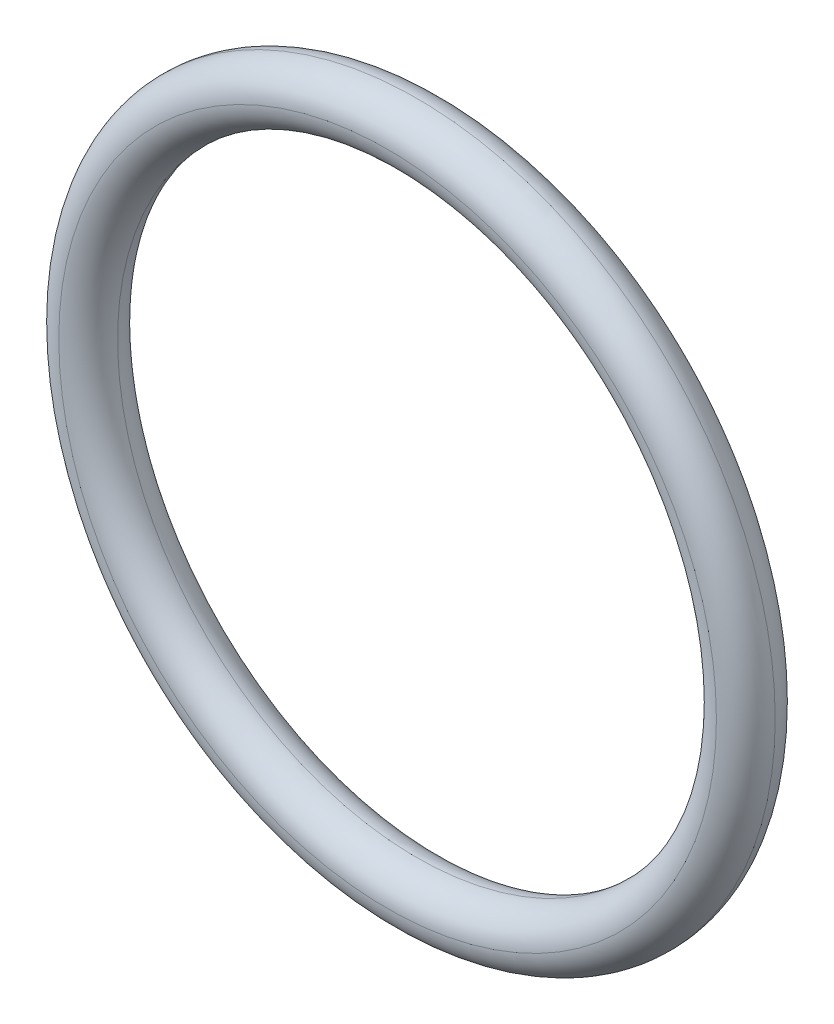
SolidWorks part; units mm, degrees
material "Caoutchouc silicone"
ref_plane "Plan de face" through (0, 0, 0) normal (0, 0, 1) x (1, 0, 0)
ref_plane "Plan de dessus" through (0, 0, 0) normal (0, 1, 0) x (1, 0, 0)
ref_plane "Plan de droite" through (0, 0, 0) normal (1, 0, 0) x (0, 0, -1)
sketch "Esquisse1" plane through (0, 0, 0) normal (0, 0, 1) x (1, 0, 0)
  circle A0 centre (0, 0) radius 37.1475
  dimension "D1" = 74.295
extrude "Boss.-Extru.1" add sketch "Esquisse1" along normal blind 6.096
sketch "Esquisse2" plane through (0, 0, 6.096) normal (0, 0, 1) x (1, 0, 0)
  circle A0 centre (0, 0) radius 31.0515
  circle A1 centre (0, 0) radius 37.1475 construction
  dimension "D1" = 6.096
extrude "Enlèv. mat.-Extru.1" cut sketch "Esquisse2" against normal through all
fillet "Congé6" radius 3.048 4 edges at (31.0515, 0, 0) (31.0515, 0, 6.096) (37.1475, 0, 0) (37.1475, 0, 6.096)
